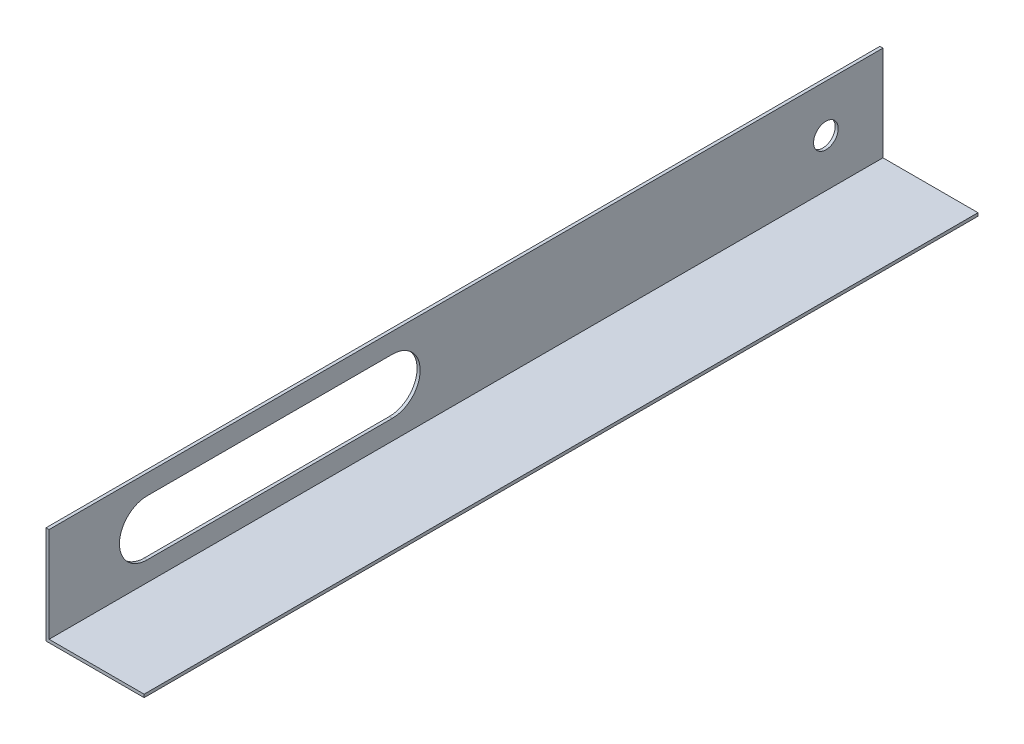
SolidWorks part; units mm, degrees
ref_plane "Front Plane" through (0, 0, 0) normal (0, 0, 1) x (1, 0, 0)
ref_plane "Top Plane" through (0, 0, 0) normal (0, 1, 0) x (1, 0, 0)
ref_plane "Right Plane" through (0, 0, 0) normal (1, 0, 0) x (0, 0, -1)
sketch "Sketch3" plane through (0, 0, 0) normal (0, 0, 1) x (1, 0, 0)
  line L0 (0, 0) -> (0, 49.2125)
  line L1 (0, 49.2125) -> (-1.5875, 49.2125)
  line L2 (-1.5875, 49.2125) -> (-1.5875, -1.5875)
  line L3 (-1.5875, -1.5875) -> (49.2125, -1.5875)
  line L4 (49.2125, -1.5875) -> (49.2125, 0)
  line L5 (49.2125, 0) -> (0, 0)
  dimension "D1" = 1.5875
  dimension "D2" = 1.5875
  dimension "D3" = 50.8
  dimension "D4" = 50.8
extrude "Boss-Extrude2" add sketch "Sketch3" along normal blind 431.8
sketch "Sketch6" plane through (0, 0, 0) normal (1, 0, 0) x (0, 0, -1)
  line L0 (-381, 24.5745) -> (-254, 24.5745) construction
  line L1 (-381, 38.9255) -> (-254, 38.9255)
  line L2 (-381, 10.2235) -> (-254, 10.2235)
  line L3 (-431.8, 0) -> (-431.8, 49.2125) construction
  line L5 (-431.8, 49.2125) -> (0, 49.2125) construction
  arc A0 (-381, 38.9255) -> (-381, 10.2235) centre (-381, 24.5745) ccw
  arc A1 (-254, 10.2235) -> (-254, 38.9255) centre (-254, 24.5745) ccw
  point P2 (-317.5, 24.5745)
  point P11 (-239.649, 24.5745)
  dimension "D3" = 50.8
  dimension "D1" = 28.702
  dimension "D2" = 127
  dimension "D4" = 24.638
extrude "Cut-Extrude3" cut sketch "Sketch6" against normal blind 127
sketch "Sketch7" plane through (0, 0, 0) normal (1, 0, 0) x (0, 0, -1)
  circle A0 centre (-29.5388, 24.7736) radius 6.3881
  dimension "D1" = 12.7762
extrude "Cut-Extrude4" cut sketch "Sketch7" against normal blind 127
